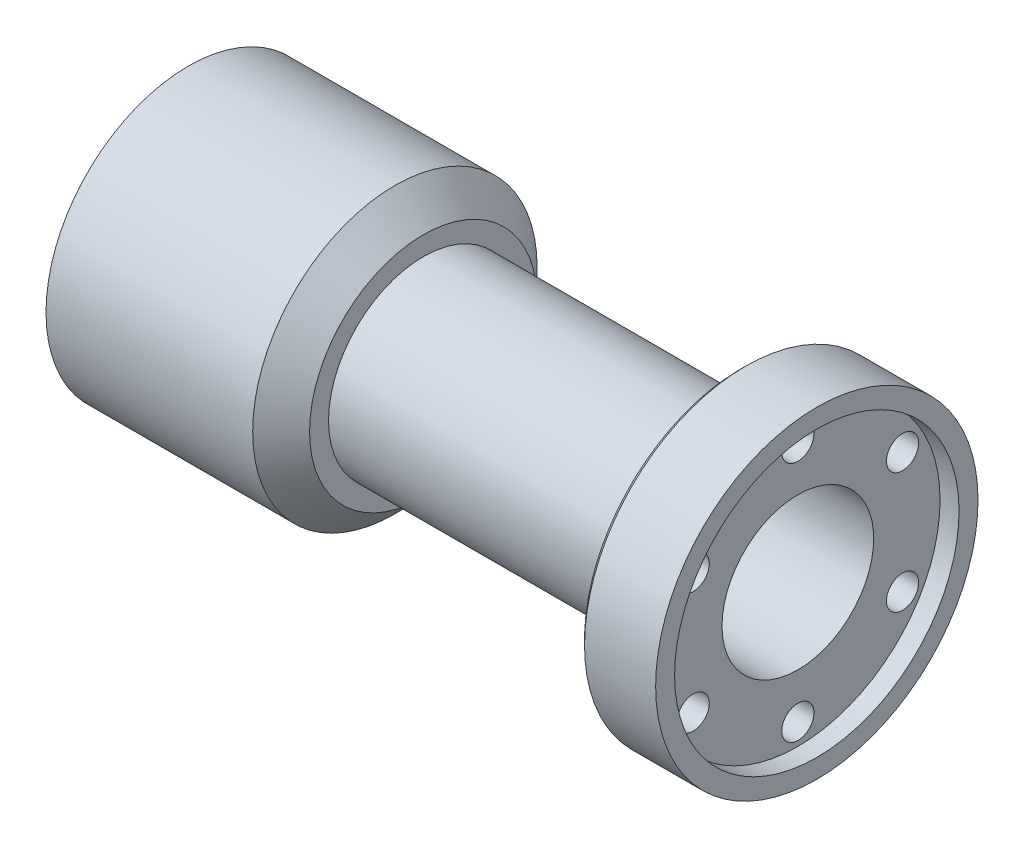
SolidWorks part; units mm, degrees
ref_plane "前视基准面" through (0, 0, 0) normal (0, 0, 1) x (1, 0, 0)
ref_plane "上视基准面" through (0, 0, 0) normal (0, 1, 0) x (1, 0, 0)
ref_plane "右视基准面" through (0, 0, 0) normal (1, 0, 0) x (0, 0, -1)
sketch "草图1" plane through (0, 0, 0) normal (0, 1, 0) x (1, 0, 0)
  line L0 (-27.6735, 0) -> (47.6327, 0) construction
  line L1 (0, 0) -> (0, 15)
  line L2 (0, 15) -> (24.8, 15)
  line L3 (24.8, 15) -> (24.8, 10)
  line L4 (24.8, 10) -> (58.3, 10)
  line L5 (58.3, 10) -> (58.3, 17)
  line L6 (58.3, 17) -> (66.3, 17)
  line L7 (66.3, 17) -> (66.3, 0)
  line L8 (66.3, 0) -> (0, 0)
  dimension "D1" = 15
  dimension "D2" = 66.3
  dimension "D3" = 24.8
  dimension "D4" = 8
  dimension "D5" = 17
  dimension "D6" = 5
revolve "旋转1" add sketch "草图1" angle 360 about L0
sketch "草图2" plane through (0, 0, 0) normal (-1, 0, 0) x (0, 0, 1)
  circle A0 centre (0, 0) radius 8
  dimension "D1" = 16
extrude "切除-拉伸1" cut sketch "草图2" against normal through all contours A0
hole_wizard "打孔尺寸(%根据)内六角圆柱头螺钉的类型1" positions "草图4" profile "草图3" counterbore size "M3" standard "GB" end condition through all
sketch "草图4" plane through (58.3, 0, 0) normal (-1, 0, 0) x (0, 0, 1)
  line L0 (0, 0) -> (0, 16.0674) construction
  circle A0 centre (0, 0) radius 12.75 construction
  point P0 (0, 12.75)
  dimension "D1" = 25.5
sketch "草图3" plane through (58.3, 12.75, 0) normal (0, 1, 0) x (0, 0, 1)
  line L0 (0, 0) -> (0, 8)
  line L1 (0, 8) -> (1.7, 8)
  line L3 (1.7, 8) -> (1.7, 3.4)
  line L4 (1.7, 3.4) -> (3, 3.4)
  line L5 (3, 3.4) -> (3, 0)
  line L7 (3, 0) -> (0, 0)
  line L11 (0, -6.35) -> (0, 107.95) construction
  dimension "通孔孔直径" = 3.4
  dimension "通孔孔深度" = 8
  dimension "柱形沉头孔直径" = 6
  dimension "柱形沉头孔深度" = 3.4
ref_axis "基准轴1" through (66.3, 0, 0) along (-1, 0, 0)
sketch "草图6" plane through (58.3, 0, 0) normal (-1, 0, 0) x (0, 0, 1)
  circle A0 centre (0, 12.75) radius 3
sketch "草图7" plane through (0, 0, 0) normal (0, 0, 1) x (1, 0, 0)
  line L0 (58.3, -10) -> (58.3, 37.8934) construction
  line L1 (0, 0) -> (89.3014, 0) construction
  line L2 (66.3, 0) -> (0, 0) construction
  line L3 (58.3, 9.9436) -> (58.3, -10) construction
  line L4 (58.3, 17) -> (58.3, -17) construction
  arc A0 (58.3, 13.9467) -> (42.0728, 27.5985) centre (58.3, 30.4168) cw
sweep "切除-扫描1" cut profiles "草图6" path "草图7"
pattern_circular "阵列(圆周)2" count 6 over 360 about axis through (66.3, 0, 0) along (-1, 0, 0) of "打孔尺寸(%根据)内六角圆柱头螺钉的类型1", "切除-扫描1"
sketch "草图5" plane through (66.3, 0, 0) normal (1, 0, 0) x (0, 0, -1)
  circle A0 centre (0, 0) radius 15
  dimension "D1" = 30
extrude "切除-拉伸2" cut sketch "草图5" against normal blind 2
chamfer "倒角1" distance 3 angle 45 1 edges at (24.8, 0, 15)
chamfer "倒角2" distance 0.5 angle 45 1 edges at (58.3, 0, 17)
hole_wizard "M4 螺纹孔1" positions "草图12" profile "草图11" tap size "M4" standard "GB"
sketch "草图12" plane through (0, 0, 0) normal (-1, 0, 0) x (0, 0, 1)
  line L1 (0, 0) -> (0, 18.1631) construction
  circle A1 centre (0, 0) radius 11.25 construction
  point P0 (0, 11.25)
  dimension "D1" = 22.5
cosmetic thread "孔螺蚊线1" parameters "D1"=5, "D2"=4
sketch "草图11" plane through (0, 11.25, 0) normal (0, 1, 0) x (0, 0, 1)
  line L0 (0, 0) -> (0, 8.0914)
  line L1 (0, 8.0914) -> (1.65, 7.1)
  line L2 (1.65, 7.1) -> (1.65, 0)
  line L5 (1.65, 0) -> (0, 0)
  line L10 (0, 8.0914) -> (-1.65, 7.1) construction
  line L11 (0, -6.35) -> (0, 107.95) construction
  dimension "螺纹孔钻头直径" = 3.3
  dimension "螺纹孔钻头深度" = 7.1
  dimension "导头角度" = 118
pattern_circular "阵列(圆周)3" count 8 over 360 about axis through (66.3, 0, 0) along (-1, 0, 0) of "M4 螺纹孔1"
